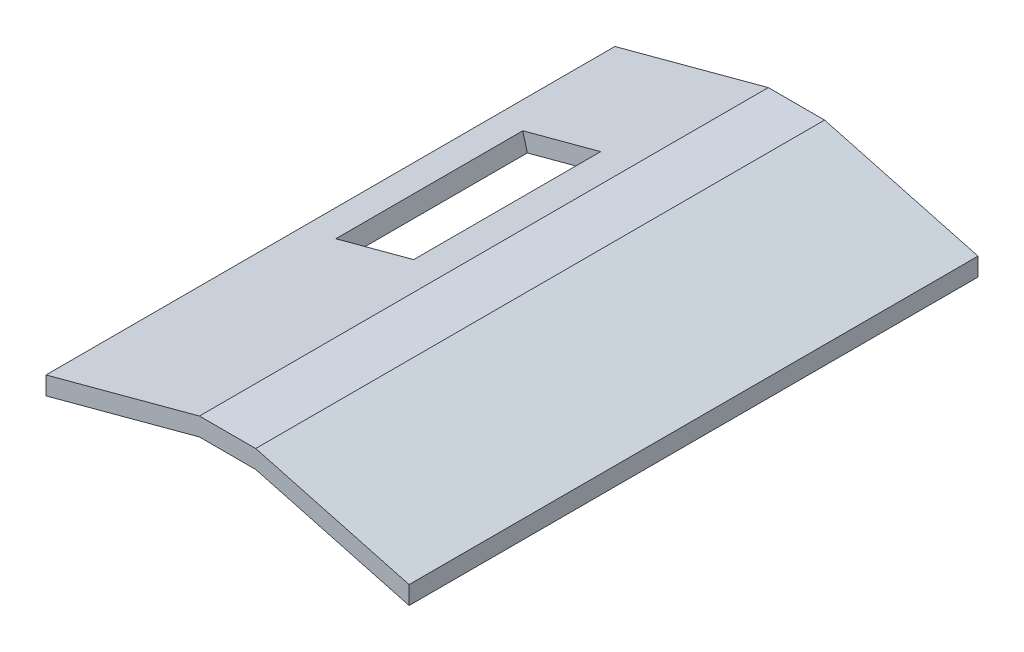
SolidWorks part; units mm, degrees
ref_plane "Ebene vorne" through (0, 0, 0) normal (0, 0, 1) x (1, 0, 0)
ref_plane "Ebene oben" through (0, 0, 0) normal (0, 1, 0) x (1, 0, 0)
ref_plane "Ebene rechts" through (0, 0, 0) normal (1, 0, 0) x (0, 0, -1)
sketch "Skizze1" plane through (0, 0, 0) normal (0, 0, 1) x (1, 0, 0)
  line L0 (650.3605, 194.2211) -> (650.3605, 144.2211)
  line L5 (650.3605, 144.2211) -> (227.8605, 257.4296)
  line L6 (227.8605, 257.4296) -> (72.8605, 257.4296)
  line L7 (72.8605, 257.4296) -> (-349.6395, 144.2211)
  line L8 (-349.6395, 144.2211) -> (-349.6395, 194.2211)
  line L9 (-349.6395, 194.2211) -> (72.8605, 307.4296)
  line L10 (72.8605, 307.4296) -> (227.8605, 307.4296)
  line L11 (227.8605, 307.4296) -> (650.3605, 194.2211)
  point P0 (0, 0)
  point P7 (650.3605, 169.2211)
  dimension "D1" = 105
  dimension "D2" = 1000
  dimension "D3" = 155
  dimension "D4" = 50
extrude "Aufsatz-Linear austragen1" add sketch "Skizze1" along normal blind 1566.7
sketch "Skizze2" plane through (-71.9767, 268.6206, 0) normal (-0.2588, 0.9659, 0) x (0.9659, 0.2588, 0)
  line L0 (-287.4577, -1566.7) -> (-287.4577, 0) construction
  line L1 (39.5423, -355) -> (-182.4577, -355)
  line L2 (39.5423, -355) -> (39.5423, -870)
  line L3 (39.5423, -870) -> (-182.4577, -870)
  line L4 (-182.4577, -355) -> (-182.4577, -870)
  line L5 (149.9465, 0) -> (-287.4577, 0) construction
  dimension "D1" = 515
  dimension "D2" = 222
  dimension "D3" = 105
  dimension "D4" = 355
extrude "Schnitt-Linear austragen1" cut sketch "Skizze2" against normal up to surface (48.2963 mm away) up to face at (-138.3895, 200.8254, 783.35)
